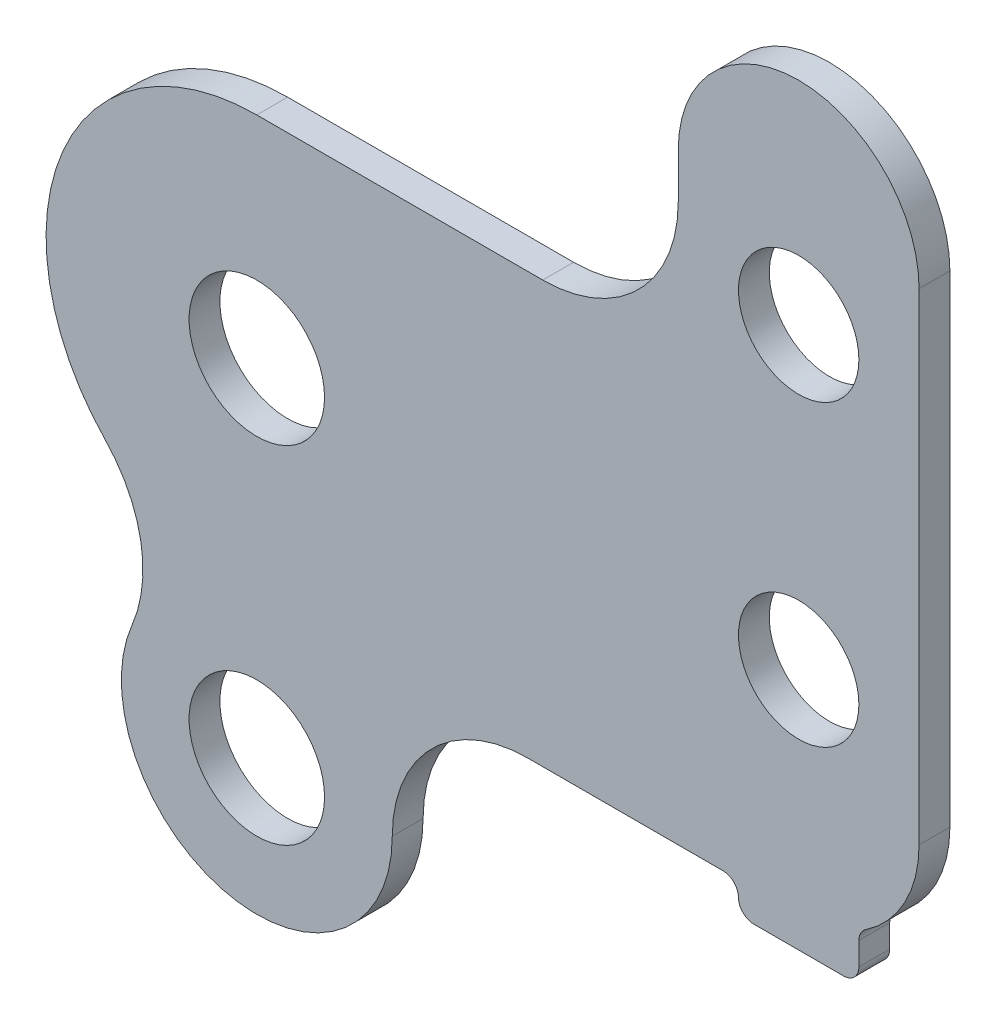
SolidWorks part; units mm, degrees
ref_plane "Front Plane" through (0, 0, 0) normal (0, 0, 1) x (1, 0, 0)
ref_plane "Top Plane" through (0, 0, 0) normal (0, 1, 0) x (1, 0, 0)
ref_plane "Right Plane" through (0, 0, 0) normal (1, 0, 0) x (0, 0, -1)
sketch "Sketch1" plane through (0, 0, 0) normal (0, 0, 1) x (1, 0, 0)
  line L2 (0, 5.5562) -> (0, -5.5562) construction
  line L6 (0, 5.5562) -> (0, -12.7) construction
  line L9 (17.4625, 13.4938) -> (11.1125, 13.4938)
  line L10 (11.1125, 13.4938) -> (11.1125, 5.5563)
  line L11 (17.4625, 13.4938) -> (17.4625, -5.5562)
  line L12 (17.4625, -5.5562) -> (0, -5.5562)
  line L13 (11.1125, 5.5563) -> (11.1125, -5.5563) construction
  line L14 (14.2875, 13.4938) -> (14.2875, -5.5563) construction
  line L15 (14.2875, 7.9058) -> (14.2875, 0.0318)
  line L16 (0, 5.5562) -> (11.1125, 5.5563)
  line L17 (15.875, -5.5563) -> (15.875, -5.1309)
  line L18 (12.7, -5.5563) -> (15.875, -5.5563)
  line L19 (12.7, -5.5563) -> (12.7, -6.3691)
  line L20 (12.7, -6.3691) -> (15.875, -6.3691)
  line L21 (15.875, -5.5563) -> (15.875, -6.3691)
  circle A0 centre (0, 0) radius 5.5562 construction
  arc A2 (0, 5.5562) -> (0, -5.5562) centre (0, 0) ccw
  circle A4 centre (0, 0) radius 1.7859
  circle A16 centre (14.2875, 7.9058) radius 1.5875
  circle A20 centre (14.2875, 0.0318) radius 1.5875
  circle A22 centre (0, 0) radius 12.7 construction
  circle A25 centre (0, 0) radius 9.1281 construction
  circle A29 centre (14.2875, 10.3188) radius 3.175
  circle A30 centre (14.2875, -2.3813) radius 3.175
  circle A32 centre (0, -9.1281) radius 3.5719
  circle A33 centre (0, -9.1281) radius 1.7859
  circle A34 centre (-6.5741, -6.3327) radius 3.5719
  circle A35 centre (7.1437, -9.1281) radius 3.5719
  point P17 (14.2875, -5.5563)
  point P20 (14.2875, 3.9688)
  point P22 (-5.2674, -7.4982)
  point P29 (6.5734, -10.0359)
  dimension "D1" = 7.874
  dimension "D2" = 11.1125
  dimension "D3" = 3.5719
  dimension "D5" = 6.35
  dimension "D6" = 7.1437
  dimension "D8" = 3.175
  dimension "D9" = 0.8128
  dimension "D11" = 3.5719
  dimension "D4" = 19.05
  dimension "D10" = 3.175
extrude "Boss-Extrude1" add sketch "Sketch1" along normal blind 0.8128 contours A30 L15 A29 L10 L16 A2 L12 A4 | A2 | L16 L10 | A30 L11 A29 L15 | A29 A16 | A30 A20 | L16 | L21 L12 L18 L19 L20 | A30 L12 L17 | A32 A33 | A35 L12 A32 | L19 L18 L21 L20 region at (14.2875, 10.7962, 0) region at (16.1269, 3.9688, 0) region at (4.7017, 0.4223, 0) region at (14.2875, -2.8587, 0) region at (15.4836, -5.4303, 0) region at (14.2875, -5.9627, 0) region at (-2.4105, -5.669, 0) region at (3.5719, -6.3541, 0) region at (2.4543, -6.6739, 0)
fillet "Fillet1" radius 0.4064 4 edges at (15.875, -5.1309, 0.4064) (15.875, -6.3691, 0.4064) (12.7, -5.5562, 0.4064) (12.7, -6.3691, 0.4064)
fillet "Fillet2" radius 3.5719 1 edges at (11.1125, 5.5563, 0.4064)
